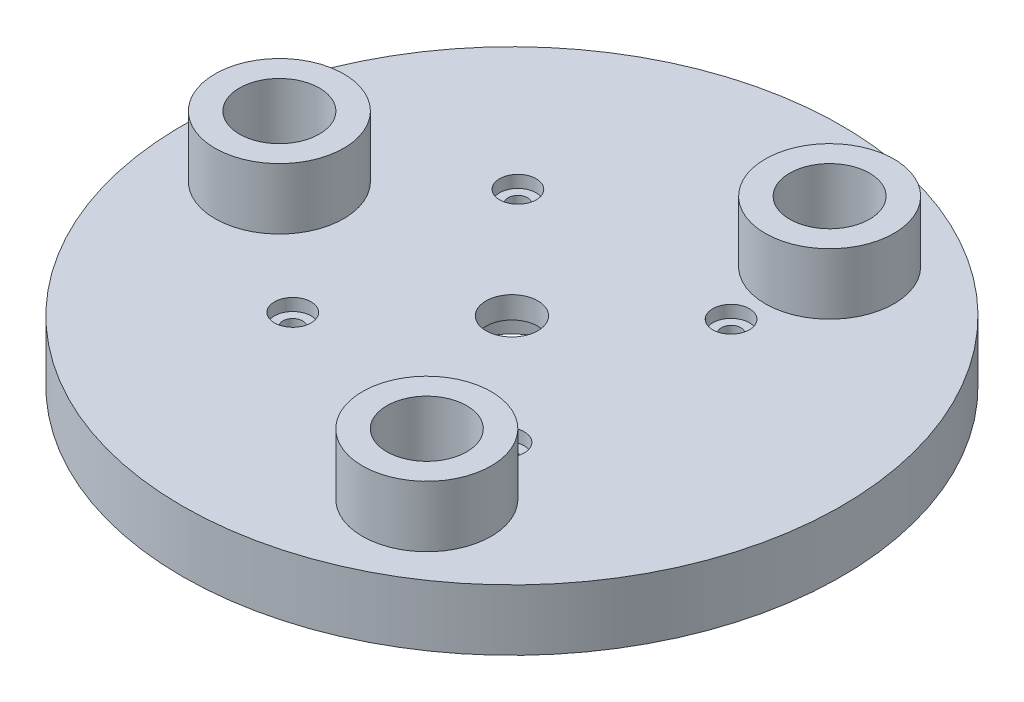
SolidWorks part; units mm, degrees
ref_plane "Front Plane" through (0, 0, 0) normal (0, 0, 1) x (1, 0, 0)
ref_plane "Top Plane" through (0, 0, 0) normal (0, 1, 0) x (1, 0, 0)
ref_plane "Right Plane" through (0, 0, 0) normal (1, 0, 0) x (0, 0, -1)
sketch "Sketch2" plane through (0, 0, 0) normal (0, 1, 0) x (1, 0, 0)
  circle A0 centre (0, 0) radius 27
  circle A1 centre (0, 0) radius 2.125
  circle A3 centre (0, 0) radius 27 construction
  point P11 (0, 0)
extrude "Boss-Extrude2" add sketch "Sketch2" along normal blind 10
sketch "Sketch3" plane through (0, 10, 0) normal (0, -1, 0) x (1, 0, 0)
  circle A3 centre (9.5263, -16.4999) radius 3.275
  circle A4 centre (9.5263, 16.4999) radius 3.275
  circle A5 centre (-19.0525, 0) radius 3.275
  circle A6 centre (9.5263, -16.4999) radius 3.175 construction
  circle A7 centre (-19.0525, 0) radius 3.175 construction
  circle A8 centre (9.5263, 16.4999) radius 3.175 construction
  dimension "D1" = 6.55
  dimension "D2" = 6.55
  dimension "D3" = 6.55
extrude "Cut-Extrude1" cut sketch "Sketch3" along normal blind 7.5
sketch "Sketch4" plane through (0, 10, 0) normal (0, 1, 0) x (1, 0, 0)
  arc A23 (-13.7775, 0) -> (-13.7775, 0) centre (-19.0525, 0) ccw
  circle A24 centre (-19.0525, 0) radius 5.275
  arc A30 (14.8013, -16.4999) -> (14.8013, -16.4999) centre (9.5263, -16.4999) ccw
  circle A31 centre (9.5263, -16.4999) radius 5.275
  circle A32 centre (0, 0) radius 27 construction
  arc A33 (14.8012, 16.4999) -> (14.8012, 16.4999) centre (9.5263, 16.4999) ccw
  circle A34 centre (9.5263, 16.4999) radius 5.275
  circle A35 centre (0, 0) radius 27
  dimension "D1" = 2
  dimension "D2" = 2
  dimension "D3" = 2
extrude "Cut-Extrude2" cut sketch "Sketch4" against normal blind 5
sketch "Sketch5" plane through (0, 0, 0) normal (0, -1, 0) x (1, 0, 0)
  line L4 (4.064, -4.065) -> (-4.064, 4.065) construction
  line L5 (-4.064, -4.065) -> (4.064, 4.065) construction
  circle A1 centre (0, 0) radius 5.25
  point P1 (0, 0)
  dimension "D3" = 10.5
  dimension "D1" = 8.13
  dimension "D2" = 8.128
extrude "Cut-Extrude3" cut sketch "Sketch5" against normal blind 3.2
sketch "Sketch6" plane through (0, 5, 0) normal (0, 1, 0) x (1, 0, 0)
  circle A0 centre (-8.7331, 9.2208) radius 0.8
  circle A1 centre (9.2208, 8.7331) radius 0.8
  circle A2 centre (8.7331, -9.2208) radius 0.8
  circle A3 centre (-9.2208, -8.7331) radius 0.8
  point P12 (0, 0)
  dimension "D1" = 12.7
  dimension "D2" = 4
extrude "Cut-Extrude4" cut sketch "Sketch6" against normal through all both and the other way through all
sketch "Sketch7" plane through (0, 5, 0) normal (0, 1, 0) x (1, 0, 0)
  circle A0 centre (-8.7331, 9.2208) radius 1.5
  circle A1 centre (9.2208, 8.7331) radius 1.5
  circle A2 centre (8.7331, -9.2208) radius 1.5
  circle A3 centre (-9.2208, -8.7331) radius 1.5
  point P12 (0, 0)
  dimension "D1" = 4
  dimension "D2" = 3
extrude "Cut-Extrude5" cut sketch "Sketch7" against normal blind 1
